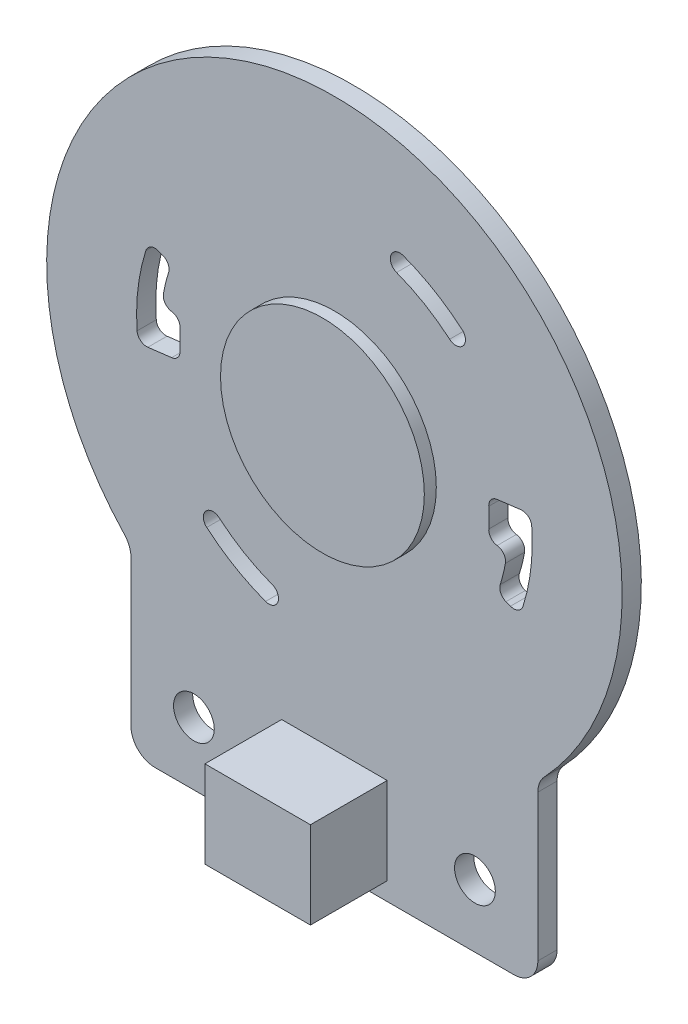
SolidWorks part; units mm, degrees
ref_plane "Front Plane" through (0, 0, 0) normal (0, 0, 1) x (1, 0, 0)
ref_plane "Top Plane" through (0, 0, 0) normal (0, 1, 0) x (1, 0, 0)
ref_plane "Right Plane" through (0, 0, 0) normal (1, 0, 0) x (0, 0, -1)
sketch "Sketch1" plane through (0, 0, 0) normal (0, 0, 1) x (1, 0, 0)
  line L0 (0, -38.4823) -> (0, 38.4823) construction
  line L1 (-18.1008, 0) -> (18.1008, 0) construction
  line L2 (15.4551, -5.7784) -> (0, 0) construction
  line L3 (16.377, 2.0108) -> (0, 0) construction
  line L4 (16.377, 2.0108) -> (12.8038, 1.5721)
  line L5 (12.8038, -1.5721) -> (0, 0) construction
  line L6 (12.8038, -1.5721) -> (14.3919, -1.7671)
  line L7 (15.4551, -5.7784) -> (13.5817, -5.078)
  line L8 (-16.9706, -16.9706) -> (0, 0) construction
  line L9 (16.9706, -16.9706) -> (0, 0) construction
  line L10 (-16.9706, -16.9706) -> (-16.9706, -29.9706)
  line L11 (16.9706, -16.9706) -> (16.9706, -29.9706)
  line L12 (-14.9706, -31.9706) -> (14.9706, -31.9706)
  line L16 (-16.377, -2.0108) -> (-12.8038, -1.5721)
  line L17 (-15.4551, 5.7784) -> (-13.5817, 5.078)
  line L18 (-12.8038, 1.5721) -> (-14.3919, 1.7671)
  line L19 (-9.6118, -11.254) -> (0, 0) construction
  line L20 (-5.1831, -13.8627) -> (0, 0) construction
  line L21 (5.4632, 14.6121) -> (0, 0) construction
  line L22 (10.1314, 11.8623) -> (0, 0) construction
  arc A0 (15.4551, -5.7784) -> (16.377, 2.0108) centre (0, 0) ccw
  arc A1 (12.8038, 1.5721) -> (12.8038, -1.5721) centre (0, 0) cw
  arc A2 (13.5817, -5.078) -> (14.3919, -1.7671) centre (0, 0) ccw
  arc A4 (16.9706, -16.9706) -> (-16.9706, -16.9706) centre (0, 0) ccw
  arc A5 (-16.9706, -29.9706) -> (-14.9706, -31.9706) centre (-14.9706, -29.9706) ccw
  arc A6 (14.9706, -31.9706) -> (16.9706, -29.9706) centre (14.9706, -29.9706) ccw
  arc A7 (-12.8038, 1.5721) -> (-12.8038, -1.5721) centre (0, 0) ccw
  arc A10 (-15.4551, 5.7784) -> (-16.377, -2.0108) centre (0, 0) ccw
  arc A11 (-13.5817, 5.078) -> (-14.3919, 1.7671) centre (0, 0) ccw
  arc A12 (-9.6118, -11.254) -> (-5.1831, -13.8627) centre (0, 0) ccw
  arc A13 (-10.6509, -12.4707) -> (-5.7434, -15.3614) centre (0, 0) ccw
  arc A14 (-9.6118, -11.254) -> (-10.6509, -12.4707) centre (-10.1314, -11.8623) ccw
  arc A15 (-5.7434, -15.3614) -> (-5.1831, -13.8627) centre (-5.4632, -14.6121) ccw
  arc A16 (5.7434, 15.3614) -> (5.1831, 13.8627) centre (5.4632, 14.6121) ccw
  arc A17 (9.6118, 11.254) -> (5.1831, 13.8627) centre (0, 0) ccw
  arc A18 (9.6118, 11.254) -> (10.6509, 12.4707) centre (10.1314, 11.8623) ccw
  arc A19 (10.6509, 12.4707) -> (5.7434, 15.3614) centre (0, 0) ccw
  point P7 (0, 0)
  point P10 (0, 0)
  point P43 (0, 0)
  dimension "D1" = 16.5
  dimension "D6" = 24
  dimension "D12" = 2
  dimension "D13" = 16.5
  dimension "D14" = 14.5
  dimension "D15" = 14.8
  dimension "D18" = 16.4
  dimension "D2" = 20.5
  dimension "D3" = 7
  dimension "D4" = 3.6
  dimension "D5" = 7
  dimension "D7" = 2
  dimension "D8" = 45
  dimension "D9" = 45
  dimension "D10" = 13
  dimension "D11" = 13
  dimension "D16" = 42.5
  dimension "D17" = 20
  dimension "D20" = 42.5
  dimension "D19" = 2
extrude "Outline" add sketch "Sketch1" along normal blind 1.6
fillet "Fillets" radius 0.8 12 edges at (16.377, 2.0108, 0.8) (12.8038, 1.5721, 0.8) (13.5817, -5.078, 0.8) (15.4551, -5.7784, 0.8) (14.3919, -1.7671, 0.8) (12.8038, -1.5721, 0.8) (-12.8038, -1.5721, 0.8) (-16.377, -2.0108, 0.8) (-15.4551, 5.7784, 0.8) (-13.5817, 5.078, 0.8) (-12.8038, 1.5721, 0.8) (-14.3919, 1.7671, 0.8)
fillet "Fillet2" radius 2 2 edges at (16.9706, -16.9706, 0.8) (-16.9706, -16.9706, 0.8)
sketch "Sketch2" plane through (0, 0, 1.6) normal (0, 0, 1) x (1, 0, 0)
  line L0 (-14.3115, 5.3508) -> (-14.6866, 5.4911) construction
  line L1 (-16.9706, -17.7797) -> (-16.9706, -29.9706) construction
  line L2 (-14.9706, -31.9706) -> (14.9706, -31.9706) construction
  line L3 (16.9706, -29.9706) -> (16.9706, -17.7797) construction
  line L4 (14.3115, -5.3508) -> (14.6866, -5.4911) construction
  line L5 (15.5627, 1.9109) -> (13.5747, 1.6668) construction
  line L6 (-15.5627, -1.9109) -> (-13.5747, -1.6668) construction
  line L7 (-16.9706, -17.7797) -> (-16.9706, -29.9706)
  line L8 (-14.9706, -31.9706) -> (14.9706, -31.9706)
  line L9 (16.9706, -29.9706) -> (16.9706, -17.7797)
  line L10 (14.3115, -5.3508) -> (14.6866, -5.4911)
  line L11 (15.5627, 1.9109) -> (13.5747, 1.6668)
  line L12 (-15.5627, -1.9109) -> (-13.5747, -1.6668)
  line L13 (-14.3115, 5.3508) -> (-14.6866, 5.4911)
  arc A0 (-14.6866, 5.4911) -> (-15.7295, 4.9834) centre (-14.9668, 4.7418) ccw construction
  arc A1 (-16.9706, -17.7797) -> (-17.5113, -16.412) centre (-18.9706, -17.7797) ccw construction
  arc A2 (-16.9706, -29.9706) -> (-14.9706, -31.9706) centre (-14.9706, -29.9706) ccw construction
  arc A3 (14.9706, -31.9706) -> (16.9706, -29.9706) centre (14.9706, -29.9706) ccw construction
  arc A4 (17.5113, -16.412) -> (16.9706, -17.7797) centre (18.9706, -17.7797) ccw construction
  arc A5 (17.5113, -16.412) -> (-17.5113, -16.412) centre (0, 0) ccw construction
  arc A6 (5.7434, 15.3614) -> (5.1831, 13.8627) centre (5.4632, 14.6121) ccw construction
  arc A7 (10.6509, 12.4707) -> (5.7434, 15.3614) centre (0, 0) ccw construction
  arc A8 (9.6118, 11.254) -> (5.1831, 13.8627) centre (0, 0) ccw construction
  arc A9 (9.6118, 11.254) -> (10.6509, 12.4707) centre (10.1314, 11.8623) ccw construction
  arc A10 (14.6866, -5.4911) -> (15.7295, -4.9834) centre (14.9668, -4.7418) ccw construction
  arc A11 (13.8287, -4.3609) -> (14.3115, -5.3508) centre (14.5916, -4.6015) ccw construction
  arc A12 (15.7295, -4.9834) -> (16.4582, 1.1737) centre (0, 0) ccw construction
  arc A13 (16.4582, 1.1737) -> (15.5627, 1.9109) centre (15.6602, 1.1168) ccw construction
  arc A14 (13.5747, 1.6668) -> (12.8738, 0.8218) centre (13.6722, 0.8727) ccw construction
  arc A15 (12.8738, -0.8218) -> (12.8738, 0.8218) centre (0, 0) ccw construction
  arc A16 (12.8738, -0.8218) -> (13.5747, -1.6668) centre (13.6722, -0.8727) ccw construction
  arc A17 (14.2642, -2.6045) -> (13.5747, -1.6668) centre (13.4772, -2.4608) ccw construction
  arc A18 (13.8287, -4.3609) -> (14.2642, -2.6045) centre (0, 0) ccw construction
  arc A19 (-9.6118, -11.254) -> (-10.6509, -12.4707) centre (-10.1314, -11.8623) ccw construction
  arc A20 (-9.6118, -11.254) -> (-5.1831, -13.8627) centre (0, 0) ccw construction
  arc A21 (-5.7434, -15.3614) -> (-5.1831, -13.8627) centre (-5.4632, -14.6121) ccw construction
  arc A22 (-10.6509, -12.4707) -> (-5.7434, -15.3614) centre (0, 0) ccw construction
  arc A23 (-14.2642, 2.6045) -> (-13.5747, 1.6668) centre (-13.4772, 2.4608) ccw construction
  arc A24 (-12.8738, 0.8218) -> (-13.5747, 1.6668) centre (-13.6722, 0.8727) ccw construction
  arc A25 (-12.8738, 0.8218) -> (-12.8738, -0.8218) centre (0, 0) ccw construction
  arc A26 (-13.5747, -1.6668) -> (-12.8738, -0.8218) centre (-13.6722, -0.8727) ccw construction
  arc A27 (-16.4582, -1.1737) -> (-15.5627, -1.9109) centre (-15.6602, -1.1168) ccw construction
  arc A28 (-15.7295, 4.9834) -> (-16.4582, -1.1737) centre (0, 0) ccw construction
  arc A29 (-13.8287, 4.3609) -> (-14.2642, 2.6045) centre (0, 0) ccw construction
  arc A30 (-13.8287, 4.3609) -> (-14.3115, 5.3508) centre (-14.5916, 4.6015) ccw construction
  arc A31 (-16.9706, -17.7797) -> (-17.5113, -16.412) centre (-18.9706, -17.7797) ccw
  arc A32 (-16.9706, -29.9706) -> (-14.9706, -31.9706) centre (-14.9706, -29.9706) ccw
  arc A33 (14.9706, -31.9706) -> (16.9706, -29.9706) centre (14.9706, -29.9706) ccw
  arc A34 (17.5113, -16.412) -> (16.9706, -17.7797) centre (18.9706, -17.7797) ccw
  arc A35 (17.5113, -16.412) -> (-17.5113, -16.412) centre (0, 0) ccw
  arc A36 (5.7434, 15.3614) -> (5.1831, 13.8627) centre (5.4632, 14.6121) ccw
  arc A37 (10.6509, 12.4707) -> (5.7434, 15.3614) centre (0, 0) ccw
  arc A38 (9.6118, 11.254) -> (5.1831, 13.8627) centre (0, 0) ccw
  arc A39 (9.6118, 11.254) -> (10.6509, 12.4707) centre (10.1314, 11.8623) ccw
  arc A40 (14.6866, -5.4911) -> (15.7295, -4.9834) centre (14.9668, -4.7418) ccw
  arc A41 (13.8287, -4.3609) -> (14.3115, -5.3508) centre (14.5916, -4.6015) ccw
  arc A42 (15.7295, -4.9834) -> (16.4582, 1.1737) centre (0, 0) ccw
  arc A43 (16.4582, 1.1737) -> (15.5627, 1.9109) centre (15.6602, 1.1168) ccw
  arc A44 (13.5747, 1.6668) -> (12.8738, 0.8218) centre (13.6722, 0.8727) ccw
  arc A45 (12.8738, -0.8218) -> (12.8738, 0.8218) centre (0, 0) ccw
  arc A46 (12.8738, -0.8218) -> (13.5747, -1.6668) centre (13.6722, -0.8727) ccw
  arc A47 (14.2642, -2.6045) -> (13.5747, -1.6668) centre (13.4772, -2.4608) ccw
  arc A48 (13.8287, -4.3609) -> (14.2642, -2.6045) centre (0, 0) ccw
  arc A49 (-9.6118, -11.254) -> (-10.6509, -12.4707) centre (-10.1314, -11.8623) ccw
  arc A50 (-9.6118, -11.254) -> (-5.1831, -13.8627) centre (0, 0) ccw
  arc A51 (-5.7434, -15.3614) -> (-5.1831, -13.8627) centre (-5.4632, -14.6121) ccw
  arc A52 (-10.6509, -12.4707) -> (-5.7434, -15.3614) centre (0, 0) ccw
  arc A53 (-14.2642, 2.6045) -> (-13.5747, 1.6668) centre (-13.4772, 2.4608) ccw
  arc A54 (-12.8738, 0.8218) -> (-13.5747, 1.6668) centre (-13.6722, 0.8727) ccw
  arc A55 (-12.8738, 0.8218) -> (-12.8738, -0.8218) centre (0, 0) ccw
  arc A56 (-13.5747, -1.6668) -> (-12.8738, -0.8218) centre (-13.6722, -0.8727) ccw
  arc A57 (-16.4582, -1.1737) -> (-15.5627, -1.9109) centre (-15.6602, -1.1168) ccw
  arc A58 (-15.7295, 4.9834) -> (-16.4582, -1.1737) centre (0, 0) ccw
  arc A59 (-13.8287, 4.3609) -> (-14.2642, 2.6045) centre (0, 0) ccw
  arc A60 (-13.8287, 4.3609) -> (-14.3115, 5.3508) centre (-14.5916, 4.6015) ccw
  arc A61 (-14.6866, 5.4911) -> (-15.7295, 4.9834) centre (-14.9668, 4.7418) ccw
sketch "Sketch3" plane through (0, 0, 1.6) normal (0, 0, 1) x (1, 0, 0)
  circle A0 centre (0, 0) radius 8.5
  dimension "D1" = 17
extrude "LED Ring Area" add sketch "Sketch3" along normal blind 1
sketch "Sketch4" plane through (0, 0, 1.6) normal (0, 0, 1) x (1, 0, 0)
  line L0 (-16.9706, -17.7797) -> (-16.9706, -29.9706) construction
  line L1 (16.9706, -29.9706) -> (16.9706, -17.7797) construction
  line L2 (-14.9706, -31.9706) -> (14.9706, -31.9706) construction
  circle A0 centre (-11.7206, -26.7206) radius 1.7
  circle A1 centre (11.7206, -26.7206) radius 1.7
  point P4 (0, 0)
  dimension "D1" = 3.4
  dimension "D2" = 5.25
  dimension "D3" = 5.25
  dimension "D4" = 5.25
extrude "Mounting Holes" cut sketch "Sketch4" against normal through all
sketch "Sketch5" plane through (0, 0, 1.6) normal (0, 0, 1) x (1, 0, 0)
  line L0 (0, 0) -> (0, -31.9706) construction
  line L1 (-4.4, -23.2206) -> (4.4, -23.2206)
  line L2 (-4.4, -23.2206) -> (-4.4, -30.4706)
  line L3 (-4.4, -30.4706) -> (4.4, -30.4706)
  line L4 (4.4, -23.2206) -> (4.4, -30.4706)
  line L5 (-14.9706, -31.9706) -> (14.9706, -31.9706) construction
  point P9 (0, -30.4706)
  dimension "D1" = 7.25
  dimension "D2" = 8.8
  dimension "D3" = 1.5
extrude "Connector Area" add sketch "Sketch5" along normal blind 6.4
